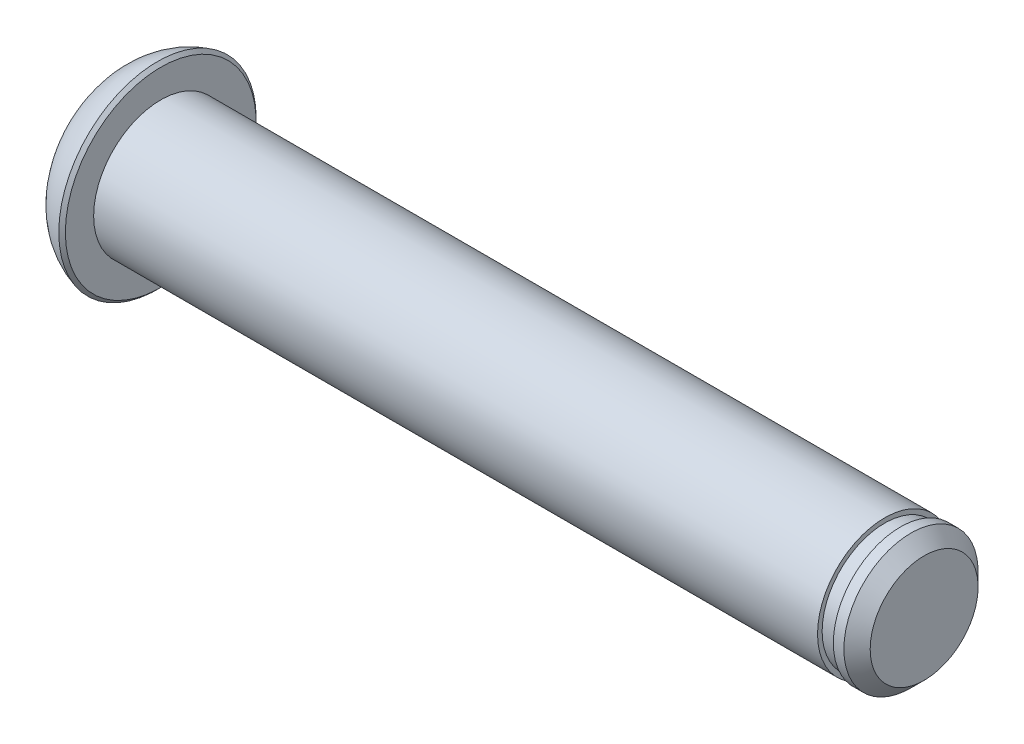
SolidWorks part; units mm, degrees
material "AISI 304"
ref_plane "Спереди" through (0, 0, 0) normal (0, 0, 1) x (1, 0, 0)
ref_plane "Сверху" through (0, 0, 0) normal (0, 1, 0) x (1, 0, 0)
ref_plane "Справа" through (0, 0, 0) normal (1, 0, 0) x (0, 0, -1)
other "Configuration Table"
sketch "Эскиз1" plane through (0, 0, 0) normal (0, 0, 1) x (1, 0, 0)
  line L0 (0, 0) -> (73.9685, 0) construction
  line L1 (0, 0) -> (0, 7.5)
  line L2 (0, 7.5) -> (4, 7.5)
  line L3 (4, 7.5) -> (4, 5.1)
  line L4 (4, 5.1) -> (62, 5.1)
  line L10 (62, 0) -> (0, 0)
  line L11 (62, 5.1) -> (62, 0)
  dimension "D1" = 10.2
  dimension "D2" = 15
  dimension "D3" = 4
  dimension "D4" = 58
revolve "Повернуть1" add sketch "Эскиз1" angle 360 about L0
chamfer "Фаска1" distance 0.25 angle 45 1 edges at (4, 0, 7.5)
sketch "Эскиз2" plane through (0, 0, 0) normal (0, 0, 1) x (1, 0, 0)
  line L0 (59, 5.1) -> (59, 4.75)
  line L1 (62, 5.1) -> (4, 5.1) construction
  line L2 (59, 4.75) -> (60.2, 4.75)
  line L3 (60.2, 4.75) -> (60.2, 5.1)
  line L4 (60.2, 5.1) -> (59, 5.1)
  line L5 (4, -7.25) -> (4, 7.25) construction
  line L6 (50, 0) -> (-50, 0) construction
  line L7 (0, 0) -> (61.9787, 0) construction
  dimension "D1" = 55
  dimension "D2" = 1.2
  dimension "D3" = 9.5
revolve "Вырез-Повернуть1" cut sketch "Эскиз2" angle 360 about L7
fillet "Скругление1" radius 5 1 edges at (0, 0, 7.5)
chamfer "Фаска2" distance 1 angle 45 1 edges at (62, 0, 5.1)
